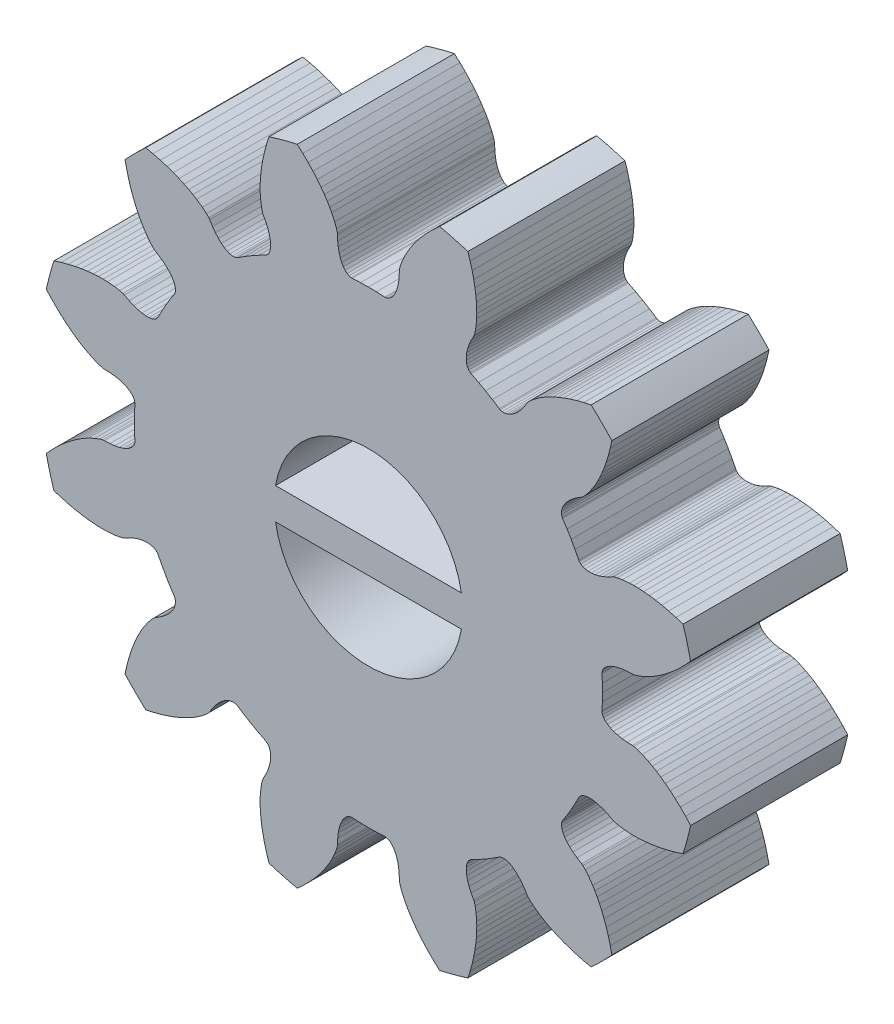
SolidWorks part; units mm, degrees
ref_plane "Płaszczyzna przednia" through (0, 0, 0) normal (0, 0, 1) x (1, 0, 0)
ref_plane "Płaszczyzna górna" through (0, 0, 0) normal (0, 1, 0) x (1, 0, 0)
ref_plane "Płaszczyzna prawa" through (0, 0, 0) normal (1, 0, 0) x (0, 0, -1)
sketch "szkic" plane through (0, 0, 0) normal (0, 0, 1) x (1, 0, 0)
  line L0 (13.3041, -6.8561) -> (13.3646, -6.6243)
  line L1 (13.3646, -6.6243) -> (13.4305, -6.4094)
  line L2 (13.4305, -6.4094) -> (13.5003, -6.2115)
  line L3 (13.5003, -6.2115) -> (13.5727, -6.0307)
  line L4 (13.5727, -6.0307) -> (13.6464, -5.8671)
  line L5 (13.6464, -5.8671) -> (13.7211, -5.718)
  line L6 (13.7211, -5.718) -> (13.7935, -5.5877)
  line L7 (13.7935, -5.5877) -> (13.8642, -5.472)
  line L8 (13.8642, -5.472) -> (13.9934, -5.2871)
  line L9 (13.9934, -5.2871) -> (14.1006, -5.158)
  line L10 (14.1006, -5.158) -> (14.1765, -5.0806)
  line L11 (14.1765, -5.0806) -> (14.2153, -5.0522)
  line L12 (14.2153, -5.0522) -> (14.3621, -4.9616)
  line L13 (14.3621, -4.9616) -> (14.4896, -4.8682)
  line L14 (14.4896, -4.8682) -> (14.5978, -4.7734)
  line L15 (14.5978, -4.7734) -> (14.6868, -4.6788)
  line L16 (14.6868, -4.6788) -> (14.7569, -4.5857)
  line L17 (14.7569, -4.5857) -> (14.8083, -4.4956)
  line L18 (14.8083, -4.4956) -> (14.8415, -4.4098)
  line L19 (14.8415, -4.4098) -> (14.8569, -4.3297)
  line L20 (14.8569, -4.3297) -> (14.8551, -4.2567)
  line L21 (14.8551, -4.2567) -> (14.8367, -4.192)
  line L22 (14.8367, -4.192) -> (14.8215, -4.1631)
  line L23 (14.8215, -4.1631) -> (14.6788, -3.9428)
  line L24 (14.6788, -3.9428) -> (14.5481, -3.725)
  line L25 (14.5481, -3.725) -> (14.4249, -3.5029)
  line L26 (14.4249, -3.5029) -> (14.3054, -3.2691)
  line L27 (14.3054, -3.2691) -> (14.288, -3.2416)
  line L28 (14.288, -3.2416) -> (14.2411, -3.1933)
  line L29 (14.2411, -3.1933) -> (14.1788, -3.1552)
  line L30 (14.1788, -3.1552) -> (14.1017, -3.1285)
  line L31 (14.1017, -3.1285) -> (14.0109, -3.1144)
  line L32 (14.0109, -3.1144) -> (13.9071, -3.1138)
  line L33 (13.9071, -3.1138) -> (13.7915, -3.128)
  line L34 (13.7915, -3.128) -> (13.665, -3.1577)
  line L35 (13.665, -3.1577) -> (13.5289, -3.2041)
  line L36 (13.5289, -3.2041) -> (13.3842, -3.2678)
  line L37 (13.3842, -3.2678) -> (13.2323, -3.3497)
  line L38 (13.2323, -3.3497) -> (13.1884, -3.369)
  line L39 (13.1884, -3.369) -> (13.0833, -3.3961)
  line L40 (13.0833, -3.3961) -> (12.918, -3.4244)
  line L41 (12.918, -3.4244) -> (12.6932, -3.4438)
  line L42 (12.6932, -3.4438) -> (12.5577, -3.4472)
  line L43 (12.5577, -3.4472) -> (12.4086, -3.4447)
  line L44 (12.4086, -3.4447) -> (12.2421, -3.4349)
  line L45 (12.2421, -3.4349) -> (12.0636, -3.4169)
  line L46 (12.0636, -3.4169) -> (11.8708, -3.3892)
  line L47 (11.8708, -3.3892) -> (11.6645, -3.3507)
  line L48 (11.6645, -3.3507) -> (11.4455, -3.3003)
  line L49 (11.4455, -3.3003) -> (11.2145, -3.2368)
  line L50 (11.2145, -3.2368) -> (10.9882, -3.1643)
  line L51 (10.7474, -2.2655) -> (10.9071, -2.0896)
  line L52 (10.9071, -2.0896) -> (11.0754, -1.9191)
  line L53 (11.0754, -1.9191) -> (11.2399, -1.7659)
  line L54 (11.2399, -1.7659) -> (11.3993, -1.6295)
  line L55 (11.3993, -1.6295) -> (11.5524, -1.5091)
  line L56 (11.5524, -1.5091) -> (11.698, -1.4042)
  line L57 (11.698, -1.4042) -> (11.8373, -1.3125)
  line L58 (11.8373, -1.3125) -> (11.9651, -1.2358)
  line L59 (11.9651, -1.2358) -> (12.0842, -1.171)
  line L60 (12.0842, -1.171) -> (12.2886, -1.0754)
  line L61 (12.2886, -1.0754) -> (12.4459, -1.0172)
  line L62 (12.4459, -1.0172) -> (12.5504, -0.9882)
  line L63 (12.5504, -0.9882) -> (12.5981, -0.983)
  line L64 (12.5981, -0.983) -> (12.7706, -0.9779)
  line L65 (12.7706, -0.9779) -> (12.9278, -0.9608)
  line L66 (12.9278, -0.9608) -> (13.0688, -0.9328)
  line L67 (13.0688, -0.9328) -> (13.1933, -0.8953)
  line L68 (13.1933, -0.8953) -> (13.3005, -0.8498)
  line L69 (13.3005, -0.8498) -> (13.3901, -0.7974)
  line L70 (13.3901, -0.7974) -> (13.4617, -0.7397)
  line L71 (13.4617, -0.7397) -> (13.515, -0.6781)
  line L72 (13.515, -0.6781) -> (13.55, -0.6139)
  line L73 (13.55, -0.6139) -> (13.5665, -0.5487)
  line L74 (13.5665, -0.5487) -> (13.5677, -0.5161)
  line L75 (13.5677, -0.5161) -> (13.5543, -0.2539)
  line L76 (13.5543, -0.2539) -> (13.55, 0)
  line L77 (13.55, 0) -> (13.5543, 0.2539)
  line L78 (13.5543, 0.2539) -> (13.5677, 0.5161)
  line L79 (13.5677, 0.5161) -> (13.5665, 0.5487)
  line L80 (13.5665, 0.5487) -> (13.55, 0.6139)
  line L81 (13.55, 0.6139) -> (13.515, 0.6781)
  line L82 (13.515, 0.6781) -> (13.4617, 0.7397)
  line L83 (13.4617, 0.7397) -> (13.3901, 0.7974)
  line L84 (13.3901, 0.7974) -> (13.3005, 0.8498)
  line L85 (13.3005, 0.8498) -> (13.1933, 0.8953)
  line L86 (13.1933, 0.8953) -> (13.0688, 0.9328)
  line L87 (13.0688, 0.9328) -> (12.9278, 0.9608)
  line L88 (12.9278, 0.9608) -> (12.7706, 0.9779)
  line L89 (12.7706, 0.9779) -> (12.5981, 0.983)
  line L90 (12.5981, 0.983) -> (12.5504, 0.9882)
  line L91 (12.5504, 0.9882) -> (12.4459, 1.0172)
  line L92 (12.4459, 1.0172) -> (12.2886, 1.0754)
  line L93 (12.2886, 1.0754) -> (12.0842, 1.171)
  line L94 (12.0842, 1.171) -> (11.9651, 1.2358)
  line L95 (11.9651, 1.2358) -> (11.8373, 1.3125)
  line L96 (11.8373, 1.3125) -> (11.698, 1.4042)
  line L97 (11.698, 1.4042) -> (11.5524, 1.5091)
  line L98 (11.5524, 1.5091) -> (11.3993, 1.6295)
  line L99 (11.3993, 1.6295) -> (11.2399, 1.7659)
  line L100 (11.2399, 1.7659) -> (11.0754, 1.9191)
  line L101 (11.0754, 1.9191) -> (10.9071, 2.0896)
  line L102 (10.9071, 2.0896) -> (10.7474, 2.2655)
  line L103 (10.9882, 3.1643) -> (11.2145, 3.2368)
  line L104 (11.2145, 3.2368) -> (11.4455, 3.3003)
  line L105 (11.4455, 3.3003) -> (11.6645, 3.3507)
  line L106 (11.6645, 3.3507) -> (11.8708, 3.3892)
  line L107 (11.8708, 3.3892) -> (12.0636, 3.4169)
  line L108 (12.0636, 3.4169) -> (12.2421, 3.4349)
  line L109 (12.2421, 3.4349) -> (12.4086, 3.4447)
  line L110 (12.4086, 3.4447) -> (12.5577, 3.4472)
  line L111 (12.5577, 3.4472) -> (12.6932, 3.4438)
  line L112 (12.6932, 3.4438) -> (12.918, 3.4244)
  line L113 (12.918, 3.4244) -> (13.0833, 3.3961)
  line L114 (13.0833, 3.3961) -> (13.1884, 3.369)
  line L115 (13.1884, 3.369) -> (13.2323, 3.3497)
  line L116 (13.2323, 3.3497) -> (13.3842, 3.2678)
  line L117 (13.3842, 3.2678) -> (13.5289, 3.2041)
  line L118 (13.5289, 3.2041) -> (13.665, 3.1577)
  line L119 (13.665, 3.1577) -> (13.7915, 3.128)
  line L120 (13.7915, 3.128) -> (13.9071, 3.1138)
  line L121 (13.9071, 3.1138) -> (14.0109, 3.1144)
  line L122 (14.0109, 3.1144) -> (14.1017, 3.1285)
  line L123 (14.1017, 3.1285) -> (14.1788, 3.1552)
  line L124 (14.1788, 3.1552) -> (14.2411, 3.1933)
  line L125 (14.2411, 3.1933) -> (14.288, 3.2416)
  line L126 (14.288, 3.2416) -> (14.3054, 3.2691)
  line L127 (14.3054, 3.2691) -> (14.4249, 3.5029)
  line L128 (14.4249, 3.5029) -> (14.5481, 3.725)
  line L129 (14.5481, 3.725) -> (14.6788, 3.9428)
  line L130 (14.6788, 3.9428) -> (14.8215, 4.1631)
  line L131 (14.8215, 4.1631) -> (14.8367, 4.192)
  line L132 (14.8367, 4.192) -> (14.8551, 4.2567)
  line L133 (14.8551, 4.2567) -> (14.8569, 4.3297)
  line L134 (14.8569, 4.3297) -> (14.8415, 4.4098)
  line L135 (14.8415, 4.4098) -> (14.8083, 4.4956)
  line L136 (14.8083, 4.4956) -> (14.7569, 4.5857)
  line L137 (14.7569, 4.5857) -> (14.6868, 4.6788)
  line L138 (14.6868, 4.6788) -> (14.5978, 4.7734)
  line L139 (14.5978, 4.7734) -> (14.4896, 4.8682)
  line L140 (14.4896, 4.8682) -> (14.3621, 4.9616)
  line L141 (14.3621, 4.9616) -> (14.2153, 5.0522)
  line L142 (14.2153, 5.0522) -> (14.1765, 5.0806)
  line L143 (14.1765, 5.0806) -> (14.1006, 5.158)
  line L144 (14.1006, 5.158) -> (13.9934, 5.2871)
  line L145 (13.9934, 5.2871) -> (13.8642, 5.472)
  line L146 (13.8642, 5.472) -> (13.7935, 5.5877)
  line L147 (13.7935, 5.5877) -> (13.7211, 5.718)
  line L148 (13.7211, 5.718) -> (13.6464, 5.8671)
  line L149 (13.6464, 5.8671) -> (13.5727, 6.0307)
  line L150 (13.5727, 6.0307) -> (13.5003, 6.2115)
  line L151 (13.5003, 6.2115) -> (13.4305, 6.4094)
  line L152 (13.4305, 6.4094) -> (13.3646, 6.6243)
  line L153 (13.3646, 6.6243) -> (13.3041, 6.8561)
  line L154 (13.3041, 6.8561) -> (13.2537, 7.0883)
  line L155 (13.9117, 7.7463) -> (14.1439, 7.6959)
  line L156 (14.1439, 7.6959) -> (14.3757, 7.6354)
  line L157 (14.3757, 7.6354) -> (14.5906, 7.5695)
  line L158 (14.5906, 7.5695) -> (14.7885, 7.4997)
  line L159 (14.7885, 7.4997) -> (14.9693, 7.4273)
  line L160 (14.9693, 7.4273) -> (15.1329, 7.3536)
  line L161 (15.1329, 7.3536) -> (15.282, 7.2789)
  line L162 (15.282, 7.2789) -> (15.4123, 7.2065)
  line L163 (15.4123, 7.2065) -> (15.528, 7.1358)
  line L164 (15.528, 7.1358) -> (15.7129, 7.0066)
  line L165 (15.7129, 7.0066) -> (15.842, 6.8994)
  line L166 (15.842, 6.8994) -> (15.9194, 6.8235)
  line L167 (15.9194, 6.8235) -> (15.9478, 6.7847)
  line L168 (15.9478, 6.7847) -> (16.0384, 6.6379)
  line L169 (16.0384, 6.6379) -> (16.1318, 6.5104)
  line L170 (16.1318, 6.5104) -> (16.2266, 6.4022)
  line L171 (16.2266, 6.4022) -> (16.3212, 6.3132)
  line L172 (16.3212, 6.3132) -> (16.4143, 6.2431)
  line L173 (16.4143, 6.2431) -> (16.5044, 6.1917)
  line L174 (16.5044, 6.1917) -> (16.5902, 6.1585)
  line L175 (16.5902, 6.1585) -> (16.6703, 6.1431)
  line L176 (16.6703, 6.1431) -> (16.7433, 6.1449)
  line L177 (16.7433, 6.1449) -> (16.808, 6.1633)
  line L178 (16.808, 6.1633) -> (16.8369, 6.1785)
  line L179 (16.8369, 6.1785) -> (17.0572, 6.3212)
  line L180 (17.0572, 6.3212) -> (17.275, 6.4519)
  line L181 (17.275, 6.4519) -> (17.4971, 6.5751)
  line L182 (17.4971, 6.5751) -> (17.7309, 6.6946)
  line L183 (17.7309, 6.6946) -> (17.7584, 6.712)
  line L184 (17.7584, 6.712) -> (17.8067, 6.7589)
  line L185 (17.8067, 6.7589) -> (17.8448, 6.8212)
  line L186 (17.8448, 6.8212) -> (17.8715, 6.8983)
  line L187 (17.8715, 6.8983) -> (17.8856, 6.9891)
  line L188 (17.8856, 6.9891) -> (17.8862, 7.0929)
  line L189 (17.8862, 7.0929) -> (17.872, 7.2085)
  line L190 (17.872, 7.2085) -> (17.8423, 7.335)
  line L191 (17.8423, 7.335) -> (17.7959, 7.4711)
  line L192 (17.7959, 7.4711) -> (17.7322, 7.6158)
  line L193 (17.7322, 7.6158) -> (17.6503, 7.7677)
  line L194 (17.6503, 7.7677) -> (17.631, 7.8116)
  line L195 (17.631, 7.8116) -> (17.6039, 7.9167)
  line L196 (17.6039, 7.9167) -> (17.5756, 8.082)
  line L197 (17.5756, 8.082) -> (17.5562, 8.3068)
  line L198 (17.5562, 8.3068) -> (17.5528, 8.4423)
  line L199 (17.5528, 8.4423) -> (17.5553, 8.5914)
  line L200 (17.5553, 8.5914) -> (17.5651, 8.7579)
  line L201 (17.5651, 8.7579) -> (17.5831, 8.9364)
  line L202 (17.5831, 8.9364) -> (17.6108, 9.1292)
  line L203 (17.6108, 9.1292) -> (17.6493, 9.3355)
  line L204 (17.6493, 9.3355) -> (17.6997, 9.5545)
  line L205 (17.6997, 9.5545) -> (17.7632, 9.7855)
  line L206 (17.7632, 9.7855) -> (17.8357, 10.0118)
  line L207 (18.7345, 10.2526) -> (18.9104, 10.0929)
  line L208 (18.9104, 10.0929) -> (19.0809, 9.9246)
  line L209 (19.0809, 9.9246) -> (19.2341, 9.7601)
  line L210 (19.2341, 9.7601) -> (19.3706, 9.6007)
  line L211 (19.3706, 9.6007) -> (19.4909, 9.4476)
  line L212 (19.4909, 9.4476) -> (19.5958, 9.302)
  line L213 (19.5958, 9.302) -> (19.6875, 9.1627)
  line L214 (19.6875, 9.1627) -> (19.7642, 9.0349)
  line L215 (19.7642, 9.0349) -> (19.829, 8.9158)
  line L216 (19.829, 8.9158) -> (19.9246, 8.7114)
  line L217 (19.9246, 8.7114) -> (19.9828, 8.5541)
  line L218 (19.9828, 8.5541) -> (20.0118, 8.4496)
  line L219 (20.0118, 8.4496) -> (20.017, 8.4019)
  line L220 (20.017, 8.4019) -> (20.0221, 8.2294)
  line L221 (20.0221, 8.2294) -> (20.0392, 8.0722)
  line L222 (20.0392, 8.0722) -> (20.0672, 7.9311)
  line L223 (20.0672, 7.9311) -> (20.1046, 7.8068)
  line L224 (20.1046, 7.8068) -> (20.1502, 7.6995)
  line L225 (20.1502, 7.6995) -> (20.2026, 7.61)
  line L226 (20.2026, 7.61) -> (20.2603, 7.5383)
  line L227 (20.2603, 7.5383) -> (20.3219, 7.485)
  line L228 (20.3219, 7.485) -> (20.3861, 7.45)
  line L229 (20.3861, 7.45) -> (20.4513, 7.4335)
  line L230 (20.4513, 7.4335) -> (20.4839, 7.4323)
  line L231 (20.4839, 7.4323) -> (20.7461, 7.4457)
  line L232 (20.7461, 7.4457) -> (21, 7.45)
  line L233 (21, 7.45) -> (21.2539, 7.4457)
  line L234 (21.2539, 7.4457) -> (21.5161, 7.4323)
  line L235 (21.5161, 7.4323) -> (21.5487, 7.4335)
  line L236 (21.5487, 7.4335) -> (21.6139, 7.45)
  line L237 (21.6139, 7.45) -> (21.6781, 7.485)
  line L238 (21.6781, 7.485) -> (21.7397, 7.5383)
  line L239 (21.7397, 7.5383) -> (21.7974, 7.61)
  line L240 (21.7974, 7.61) -> (21.8498, 7.6995)
  line L241 (21.8498, 7.6995) -> (21.8954, 7.8068)
  line L242 (21.8954, 7.8068) -> (21.9328, 7.9311)
  line L243 (21.9328, 7.9311) -> (21.9608, 8.0722)
  line L244 (21.9608, 8.0722) -> (21.9779, 8.2294)
  line L245 (21.9779, 8.2294) -> (21.983, 8.4019)
  line L246 (21.983, 8.4019) -> (21.9882, 8.4496)
  line L247 (21.9882, 8.4496) -> (22.0172, 8.5541)
  line L248 (22.0172, 8.5541) -> (22.0754, 8.7114)
  line L249 (22.0754, 8.7114) -> (22.171, 8.9158)
  line L250 (22.171, 8.9158) -> (22.2358, 9.0349)
  line L251 (22.2358, 9.0349) -> (22.3125, 9.1627)
  line L252 (22.3125, 9.1627) -> (22.4042, 9.302)
  line L253 (22.4042, 9.302) -> (22.5091, 9.4476)
  line L254 (22.5091, 9.4476) -> (22.6294, 9.6007)
  line L255 (22.6294, 9.6007) -> (22.7659, 9.7601)
  line L256 (22.7659, 9.7601) -> (22.9191, 9.9246)
  line L257 (22.9191, 9.9246) -> (23.0896, 10.0929)
  line L258 (23.0896, 10.0929) -> (23.2655, 10.2526)
  line L259 (24.1643, 10.0118) -> (24.2368, 9.7855)
  line L260 (24.2368, 9.7855) -> (24.3003, 9.5545)
  line L261 (24.3003, 9.5545) -> (24.3507, 9.3355)
  line L262 (24.3507, 9.3355) -> (24.3892, 9.1292)
  line L263 (24.3892, 9.1292) -> (24.4169, 8.9364)
  line L264 (24.4169, 8.9364) -> (24.4349, 8.7579)
  line L265 (24.4349, 8.7579) -> (24.4447, 8.5914)
  line L266 (24.4447, 8.5914) -> (24.4472, 8.4423)
  line L267 (24.4472, 8.4423) -> (24.4438, 8.3068)
  line L268 (24.4438, 8.3068) -> (24.4244, 8.082)
  line L269 (24.4244, 8.082) -> (24.3961, 7.9167)
  line L270 (24.3961, 7.9167) -> (24.369, 7.8116)
  line L271 (24.369, 7.8116) -> (24.3497, 7.7677)
  line L272 (24.3497, 7.7677) -> (24.2678, 7.6158)
  line L273 (24.2678, 7.6158) -> (24.2041, 7.4711)
  line L274 (24.2041, 7.4711) -> (24.1577, 7.335)
  line L275 (24.1577, 7.335) -> (24.128, 7.2085)
  line L276 (24.128, 7.2085) -> (24.1138, 7.0929)
  line L277 (24.1138, 7.0929) -> (24.1144, 6.9891)
  line L278 (24.1144, 6.9891) -> (24.1285, 6.8983)
  line L279 (24.1285, 6.8983) -> (24.1552, 6.8212)
  line L280 (24.1552, 6.8212) -> (24.1933, 6.7589)
  line L281 (24.1933, 6.7589) -> (24.2416, 6.712)
  line L282 (24.2416, 6.712) -> (24.2691, 6.6946)
  line L283 (24.2691, 6.6946) -> (24.5029, 6.5751)
  line L284 (24.5029, 6.5751) -> (24.725, 6.4519)
  line L285 (24.725, 6.4519) -> (24.9428, 6.3212)
  line L286 (24.9428, 6.3212) -> (25.1631, 6.1785)
  line L287 (25.1631, 6.1785) -> (25.192, 6.1633)
  line L288 (25.192, 6.1633) -> (25.2567, 6.1449)
  line L289 (25.2567, 6.1449) -> (25.3297, 6.1431)
  line L290 (25.3297, 6.1431) -> (25.4098, 6.1585)
  line L291 (25.4098, 6.1585) -> (25.4956, 6.1917)
  line L292 (25.4956, 6.1917) -> (25.5857, 6.2431)
  line L293 (25.5857, 6.2431) -> (25.6788, 6.3132)
  line L294 (25.6788, 6.3132) -> (25.7734, 6.4022)
  line L295 (25.7734, 6.4022) -> (25.8682, 6.5104)
  line L296 (25.8682, 6.5104) -> (25.9616, 6.6379)
  line L297 (25.9616, 6.6379) -> (26.0522, 6.7847)
  line L298 (26.0522, 6.7847) -> (26.0806, 6.8235)
  line L299 (26.0806, 6.8235) -> (26.158, 6.8994)
  line L300 (26.158, 6.8994) -> (26.2871, 7.0066)
  line L301 (26.2871, 7.0066) -> (26.472, 7.1358)
  line L302 (26.472, 7.1358) -> (26.5877, 7.2065)
  line L303 (26.5877, 7.2065) -> (26.718, 7.2789)
  line L304 (26.718, 7.2789) -> (26.8671, 7.3536)
  line L305 (26.8671, 7.3536) -> (27.0307, 7.4273)
  line L306 (27.0307, 7.4273) -> (27.2115, 7.4997)
  line L307 (27.2115, 7.4997) -> (27.4094, 7.5695)
  line L308 (27.4094, 7.5695) -> (27.6243, 7.6354)
  line L309 (27.6243, 7.6354) -> (27.8561, 7.6959)
  line L310 (27.8561, 7.6959) -> (28.0883, 7.7463)
  line L311 (28.7463, 7.0883) -> (28.6959, 6.8561)
  line L312 (28.6959, 6.8561) -> (28.6354, 6.6243)
  line L313 (28.6354, 6.6243) -> (28.5695, 6.4094)
  line L314 (28.5695, 6.4094) -> (28.4997, 6.2115)
  line L315 (28.4997, 6.2115) -> (28.4273, 6.0307)
  line L316 (28.4273, 6.0307) -> (28.3536, 5.8671)
  line L317 (28.3536, 5.8671) -> (28.2789, 5.718)
  line L318 (28.2789, 5.718) -> (28.2065, 5.5877)
  line L319 (28.2065, 5.5877) -> (28.1358, 5.472)
  line L320 (28.1358, 5.472) -> (28.0066, 5.2871)
  line L321 (28.0066, 5.2871) -> (27.8994, 5.158)
  line L322 (27.8994, 5.158) -> (27.8235, 5.0806)
  line L323 (27.8235, 5.0806) -> (27.7847, 5.0522)
  line L324 (27.7847, 5.0522) -> (27.6379, 4.9616)
  line L325 (27.6379, 4.9616) -> (27.5104, 4.8682)
  line L326 (27.5104, 4.8682) -> (27.4022, 4.7734)
  line L327 (27.4022, 4.7734) -> (27.3132, 4.6788)
  line L328 (27.3132, 4.6788) -> (27.2431, 4.5857)
  line L329 (27.2431, 4.5857) -> (27.1917, 4.4956)
  line L330 (27.1917, 4.4956) -> (27.1585, 4.4098)
  line L331 (27.1585, 4.4098) -> (27.1431, 4.3297)
  line L332 (27.1431, 4.3297) -> (27.1449, 4.2567)
  line L333 (27.1449, 4.2567) -> (27.1633, 4.192)
  line L334 (27.1633, 4.192) -> (27.1785, 4.1631)
  line L335 (27.1785, 4.1631) -> (27.3212, 3.9428)
  line L336 (27.3212, 3.9428) -> (27.4519, 3.725)
  line L337 (27.4519, 3.725) -> (27.5751, 3.5029)
  line L338 (27.5751, 3.5029) -> (27.6946, 3.2691)
  line L339 (27.6946, 3.2691) -> (27.712, 3.2416)
  line L340 (27.712, 3.2416) -> (27.7589, 3.1933)
  line L341 (27.7589, 3.1933) -> (27.8212, 3.1552)
  line L342 (27.8212, 3.1552) -> (27.8983, 3.1285)
  line L343 (27.8983, 3.1285) -> (27.9891, 3.1144)
  line L344 (27.9891, 3.1144) -> (28.0929, 3.1138)
  line L345 (28.0929, 3.1138) -> (28.2085, 3.128)
  line L346 (28.2085, 3.128) -> (28.335, 3.1577)
  line L347 (28.335, 3.1577) -> (28.4711, 3.2041)
  line L348 (28.4711, 3.2041) -> (28.6158, 3.2678)
  line L349 (28.6158, 3.2678) -> (28.7677, 3.3497)
  line L350 (28.7677, 3.3497) -> (28.8116, 3.369)
  line L351 (28.8116, 3.369) -> (28.9167, 3.3961)
  line L352 (28.9167, 3.3961) -> (29.082, 3.4244)
  line L353 (29.082, 3.4244) -> (29.3068, 3.4438)
  line L354 (29.3068, 3.4438) -> (29.4423, 3.4472)
  line L355 (29.4423, 3.4472) -> (29.5914, 3.4447)
  line L356 (29.5914, 3.4447) -> (29.7579, 3.4349)
  line L357 (29.7579, 3.4349) -> (29.9364, 3.4169)
  line L358 (29.9364, 3.4169) -> (30.1292, 3.3892)
  line L359 (30.1292, 3.3892) -> (30.3355, 3.3507)
  line L360 (30.3355, 3.3507) -> (30.5545, 3.3003)
  line L361 (30.5545, 3.3003) -> (30.7855, 3.2368)
  line L362 (30.7855, 3.2368) -> (31.0118, 3.1643)
  line L363 (31.2526, 2.2655) -> (31.0929, 2.0896)
  line L364 (31.0929, 2.0896) -> (30.9246, 1.9191)
  line L365 (30.9246, 1.9191) -> (30.7601, 1.7659)
  line L366 (30.7601, 1.7659) -> (30.6007, 1.6295)
  line L367 (30.6007, 1.6295) -> (30.4476, 1.5091)
  line L368 (30.4476, 1.5091) -> (30.302, 1.4042)
  line L369 (30.302, 1.4042) -> (30.1627, 1.3125)
  line L370 (30.1627, 1.3125) -> (30.0349, 1.2358)
  line L371 (30.0349, 1.2358) -> (29.9158, 1.171)
  line L372 (29.9158, 1.171) -> (29.7114, 1.0754)
  line L373 (29.7114, 1.0754) -> (29.5541, 1.0172)
  line L374 (29.5541, 1.0172) -> (29.4496, 0.9882)
  line L375 (29.4496, 0.9882) -> (29.4019, 0.983)
  line L376 (29.4019, 0.983) -> (29.2294, 0.9779)
  line L377 (29.2294, 0.9779) -> (29.0722, 0.9608)
  line L378 (29.0722, 0.9608) -> (28.9311, 0.9328)
  line L379 (28.9311, 0.9328) -> (28.8068, 0.8953)
  line L380 (28.8068, 0.8953) -> (28.6995, 0.8498)
  line L381 (28.6995, 0.8498) -> (28.61, 0.7974)
  line L382 (28.61, 0.7974) -> (28.5383, 0.7397)
  line L383 (28.5383, 0.7397) -> (28.485, 0.6781)
  line L384 (28.485, 0.6781) -> (28.45, 0.6139)
  line L385 (28.45, 0.6139) -> (28.4335, 0.5487)
  line L386 (28.4335, 0.5487) -> (28.4323, 0.5161)
  line L387 (28.4323, 0.5161) -> (28.4457, 0.2539)
  line L388 (28.4457, 0.2539) -> (28.45, 0)
  line L389 (28.45, 0) -> (28.4457, -0.2539)
  line L390 (28.4457, -0.2539) -> (28.4323, -0.5161)
  line L391 (28.4323, -0.5161) -> (28.4335, -0.5487)
  line L392 (28.4335, -0.5487) -> (28.45, -0.6139)
  line L393 (28.45, -0.6139) -> (28.485, -0.6781)
  line L394 (28.485, -0.6781) -> (28.5383, -0.7397)
  line L395 (28.5383, -0.7397) -> (28.61, -0.7974)
  line L396 (28.61, -0.7974) -> (28.6995, -0.8498)
  line L397 (28.6995, -0.8498) -> (28.8068, -0.8953)
  line L398 (28.8068, -0.8953) -> (28.9311, -0.9328)
  line L399 (28.9311, -0.9328) -> (29.0722, -0.9608)
  line L400 (29.0722, -0.9608) -> (29.2294, -0.9779)
  line L401 (29.2294, -0.9779) -> (29.4019, -0.983)
  line L402 (29.4019, -0.983) -> (29.4496, -0.9882)
  line L403 (29.4496, -0.9882) -> (29.5541, -1.0172)
  line L404 (29.5541, -1.0172) -> (29.7114, -1.0754)
  line L405 (29.7114, -1.0754) -> (29.9158, -1.171)
  line L406 (29.9158, -1.171) -> (30.0349, -1.2358)
  line L407 (30.0349, -1.2358) -> (30.1627, -1.3125)
  line L408 (30.1627, -1.3125) -> (30.302, -1.4042)
  line L409 (30.302, -1.4042) -> (30.4476, -1.5091)
  line L410 (30.4476, -1.5091) -> (30.6007, -1.6295)
  line L411 (30.6007, -1.6295) -> (30.7601, -1.7659)
  line L412 (30.7601, -1.7659) -> (30.9246, -1.9191)
  line L413 (30.9246, -1.9191) -> (31.0929, -2.0896)
  line L414 (31.0929, -2.0896) -> (31.2526, -2.2655)
  line L415 (31.0118, -3.1643) -> (30.7855, -3.2368)
  line L416 (30.7855, -3.2368) -> (30.5545, -3.3003)
  line L417 (30.5545, -3.3003) -> (30.3355, -3.3507)
  line L418 (30.3355, -3.3507) -> (30.1292, -3.3892)
  line L419 (30.1292, -3.3892) -> (29.9364, -3.4169)
  line L420 (29.9364, -3.4169) -> (29.7579, -3.4349)
  line L421 (29.7579, -3.4349) -> (29.5914, -3.4447)
  line L422 (29.5914, -3.4447) -> (29.4423, -3.4472)
  line L423 (29.4423, -3.4472) -> (29.3068, -3.4438)
  line L424 (29.3068, -3.4438) -> (29.082, -3.4244)
  line L425 (29.082, -3.4244) -> (28.9167, -3.3961)
  line L426 (28.9167, -3.3961) -> (28.8116, -3.369)
  line L427 (28.8116, -3.369) -> (28.7677, -3.3497)
  line L428 (28.7677, -3.3497) -> (28.6158, -3.2678)
  line L429 (28.6158, -3.2678) -> (28.4711, -3.2041)
  line L430 (28.4711, -3.2041) -> (28.335, -3.1577)
  line L431 (28.335, -3.1577) -> (28.2085, -3.128)
  line L432 (28.2085, -3.128) -> (28.0929, -3.1138)
  line L433 (28.0929, -3.1138) -> (27.9891, -3.1144)
  line L434 (27.9891, -3.1144) -> (27.8983, -3.1285)
  line L435 (27.8983, -3.1285) -> (27.8212, -3.1552)
  line L436 (27.8212, -3.1552) -> (27.7589, -3.1933)
  line L437 (27.7589, -3.1933) -> (27.712, -3.2416)
  line L438 (27.712, -3.2416) -> (27.6946, -3.2691)
  line L439 (27.6946, -3.2691) -> (27.5751, -3.5029)
  line L440 (27.5751, -3.5029) -> (27.4519, -3.725)
  line L441 (27.4519, -3.725) -> (27.3212, -3.9428)
  line L442 (27.3212, -3.9428) -> (27.1785, -4.1631)
  line L443 (27.1785, -4.1631) -> (27.1633, -4.192)
  line L444 (27.1633, -4.192) -> (27.1449, -4.2567)
  line L445 (27.1449, -4.2567) -> (27.1431, -4.3297)
  line L446 (27.1431, -4.3297) -> (27.1585, -4.4098)
  line L447 (27.1585, -4.4098) -> (27.1917, -4.4956)
  line L448 (27.1917, -4.4956) -> (27.2431, -4.5857)
  line L449 (27.2431, -4.5857) -> (27.3132, -4.6788)
  line L450 (27.3132, -4.6788) -> (27.4022, -4.7734)
  line L451 (27.4022, -4.7734) -> (27.5104, -4.8682)
  line L452 (27.5104, -4.8682) -> (27.6379, -4.9616)
  line L453 (27.6379, -4.9616) -> (27.7847, -5.0522)
  line L454 (27.7847, -5.0522) -> (27.8235, -5.0806)
  line L455 (27.8235, -5.0806) -> (27.8994, -5.158)
  line L456 (27.8994, -5.158) -> (28.0066, -5.2871)
  line L457 (28.0066, -5.2871) -> (28.1358, -5.472)
  line L458 (28.1358, -5.472) -> (28.2065, -5.5877)
  line L459 (28.2065, -5.5877) -> (28.2789, -5.718)
  line L460 (28.2789, -5.718) -> (28.3536, -5.8671)
  line L461 (28.3536, -5.8671) -> (28.4273, -6.0307)
  line L462 (28.4273, -6.0307) -> (28.4997, -6.2115)
  line L463 (28.4997, -6.2115) -> (28.5695, -6.4094)
  line L464 (28.5695, -6.4094) -> (28.6354, -6.6243)
  line L465 (28.6354, -6.6243) -> (28.6959, -6.8561)
  line L466 (28.6959, -6.8561) -> (28.7463, -7.0883)
  line L467 (28.0883, -7.7463) -> (27.8561, -7.6959)
  line L468 (27.8561, -7.6959) -> (27.6243, -7.6354)
  line L469 (27.6243, -7.6354) -> (27.4094, -7.5695)
  line L470 (27.4094, -7.5695) -> (27.2115, -7.4997)
  line L471 (27.2115, -7.4997) -> (27.0307, -7.4273)
  line L472 (27.0307, -7.4273) -> (26.8671, -7.3536)
  line L473 (26.8671, -7.3536) -> (26.718, -7.2789)
  line L474 (26.718, -7.2789) -> (26.5877, -7.2065)
  line L475 (26.5877, -7.2065) -> (26.472, -7.1358)
  line L476 (26.472, -7.1358) -> (26.2871, -7.0066)
  line L477 (26.2871, -7.0066) -> (26.158, -6.8994)
  line L478 (26.158, -6.8994) -> (26.0806, -6.8235)
  line L479 (26.0806, -6.8235) -> (26.0522, -6.7847)
  line L480 (26.0522, -6.7847) -> (25.9616, -6.6379)
  line L481 (25.9616, -6.6379) -> (25.8682, -6.5104)
  line L482 (25.8682, -6.5104) -> (25.7734, -6.4022)
  line L483 (25.7734, -6.4022) -> (25.6788, -6.3132)
  line L484 (25.6788, -6.3132) -> (25.5857, -6.2431)
  line L485 (25.5857, -6.2431) -> (25.4956, -6.1917)
  line L486 (25.4956, -6.1917) -> (25.4098, -6.1585)
  line L487 (25.4098, -6.1585) -> (25.3297, -6.1431)
  line L488 (25.3297, -6.1431) -> (25.2567, -6.1449)
  line L489 (25.2567, -6.1449) -> (25.192, -6.1633)
  line L490 (25.192, -6.1633) -> (25.1631, -6.1785)
  line L491 (25.1631, -6.1785) -> (24.9428, -6.3212)
  line L492 (24.9428, -6.3212) -> (24.725, -6.4519)
  line L493 (24.725, -6.4519) -> (24.5029, -6.5751)
  line L494 (24.5029, -6.5751) -> (24.2691, -6.6946)
  line L495 (24.2691, -6.6946) -> (24.2416, -6.712)
  line L496 (24.2416, -6.712) -> (24.1933, -6.7589)
  line L497 (24.1933, -6.7589) -> (24.1552, -6.8212)
  line L498 (24.1552, -6.8212) -> (24.1285, -6.8983)
  line L499 (24.1285, -6.8983) -> (24.1144, -6.9891)
  line L500 (24.1144, -6.9891) -> (24.1138, -7.0929)
  line L501 (24.1138, -7.0929) -> (24.128, -7.2085)
  line L502 (24.128, -7.2085) -> (24.1577, -7.335)
  line L503 (24.1577, -7.335) -> (24.2041, -7.4711)
  line L504 (24.2041, -7.4711) -> (24.2678, -7.6158)
  line L505 (24.2678, -7.6158) -> (24.3497, -7.7677)
  line L506 (24.3497, -7.7677) -> (24.369, -7.8116)
  line L507 (24.369, -7.8116) -> (24.3961, -7.9167)
  line L508 (24.3961, -7.9167) -> (24.4244, -8.082)
  line L509 (24.4244, -8.082) -> (24.4438, -8.3068)
  line L510 (24.4438, -8.3068) -> (24.4472, -8.4423)
  line L511 (24.4472, -8.4423) -> (24.4447, -8.5914)
  line L512 (24.4447, -8.5914) -> (24.4349, -8.7579)
  line L513 (24.4349, -8.7579) -> (24.4169, -8.9364)
  line L514 (24.4169, -8.9364) -> (24.3892, -9.1292)
  line L515 (24.3892, -9.1292) -> (24.3507, -9.3355)
  line L516 (24.3507, -9.3355) -> (24.3003, -9.5545)
  line L517 (24.3003, -9.5545) -> (24.2368, -9.7855)
  line L518 (24.2368, -9.7855) -> (24.1643, -10.0118)
  line L519 (23.2655, -10.2526) -> (23.0896, -10.0929)
  line L520 (23.0896, -10.0929) -> (22.9191, -9.9246)
  line L521 (22.9191, -9.9246) -> (22.7659, -9.7601)
  line L522 (22.7659, -9.7601) -> (22.6294, -9.6007)
  line L523 (22.6294, -9.6007) -> (22.5091, -9.4476)
  line L524 (22.5091, -9.4476) -> (22.4042, -9.302)
  line L525 (22.4042, -9.302) -> (22.3125, -9.1627)
  line L526 (22.3125, -9.1627) -> (22.2358, -9.0349)
  line L527 (22.2358, -9.0349) -> (22.171, -8.9158)
  line L528 (22.171, -8.9158) -> (22.0754, -8.7114)
  line L529 (22.0754, -8.7114) -> (22.0172, -8.5541)
  line L530 (22.0172, -8.5541) -> (21.9882, -8.4496)
  line L531 (21.9882, -8.4496) -> (21.983, -8.4019)
  line L532 (21.983, -8.4019) -> (21.9779, -8.2294)
  line L533 (21.9779, -8.2294) -> (21.9608, -8.0722)
  line L534 (21.9608, -8.0722) -> (21.9328, -7.9311)
  line L535 (21.9328, -7.9311) -> (21.8954, -7.8068)
  line L536 (21.8954, -7.8068) -> (21.8498, -7.6995)
  line L537 (21.8498, -7.6995) -> (21.7974, -7.61)
  line L538 (21.7974, -7.61) -> (21.7397, -7.5383)
  line L539 (21.7397, -7.5383) -> (21.6781, -7.485)
  line L540 (21.6781, -7.485) -> (21.6139, -7.45)
  line L541 (21.6139, -7.45) -> (21.5487, -7.4335)
  line L542 (21.5487, -7.4335) -> (21.5161, -7.4323)
  line L543 (21.5161, -7.4323) -> (21.2539, -7.4457)
  line L544 (21.2539, -7.4457) -> (21, -7.45)
  line L545 (21, -7.45) -> (20.7461, -7.4457)
  line L546 (20.7461, -7.4457) -> (20.4839, -7.4323)
  line L547 (20.4839, -7.4323) -> (20.4513, -7.4335)
  line L548 (20.4513, -7.4335) -> (20.3861, -7.45)
  line L549 (20.3861, -7.45) -> (20.3219, -7.485)
  line L550 (20.3219, -7.485) -> (20.2603, -7.5383)
  line L551 (20.2603, -7.5383) -> (20.2026, -7.61)
  line L552 (20.2026, -7.61) -> (20.1502, -7.6995)
  line L553 (20.1502, -7.6995) -> (20.1046, -7.8068)
  line L554 (20.1046, -7.8068) -> (20.0672, -7.9311)
  line L555 (20.0672, -7.9311) -> (20.0392, -8.0722)
  line L556 (20.0392, -8.0722) -> (20.0221, -8.2294)
  line L557 (20.0221, -8.2294) -> (20.017, -8.4019)
  line L558 (20.017, -8.4019) -> (20.0118, -8.4496)
  line L559 (20.0118, -8.4496) -> (19.9828, -8.5541)
  line L560 (19.9828, -8.5541) -> (19.9246, -8.7114)
  line L561 (19.9246, -8.7114) -> (19.829, -8.9158)
  line L562 (19.829, -8.9158) -> (19.7642, -9.0349)
  line L563 (19.7642, -9.0349) -> (19.6875, -9.1627)
  line L564 (19.6875, -9.1627) -> (19.5958, -9.302)
  line L565 (19.5958, -9.302) -> (19.4909, -9.4476)
  line L566 (19.4909, -9.4476) -> (19.3706, -9.6007)
  line L567 (19.3706, -9.6007) -> (19.2341, -9.7601)
  line L568 (19.2341, -9.7601) -> (19.0809, -9.9246)
  line L569 (19.0809, -9.9246) -> (18.9104, -10.0929)
  line L570 (18.9104, -10.0929) -> (18.7345, -10.2526)
  line L571 (17.8357, -10.0118) -> (17.7632, -9.7855)
  line L572 (17.7632, -9.7855) -> (17.6997, -9.5545)
  line L573 (17.6997, -9.5545) -> (17.6493, -9.3355)
  line L574 (17.6493, -9.3355) -> (17.6108, -9.1292)
  line L575 (17.6108, -9.1292) -> (17.5831, -8.9364)
  line L576 (17.5831, -8.9364) -> (17.5651, -8.7579)
  line L577 (17.5651, -8.7579) -> (17.5553, -8.5914)
  line L578 (17.5553, -8.5914) -> (17.5528, -8.4423)
  line L579 (17.5528, -8.4423) -> (17.5562, -8.3068)
  line L580 (17.5562, -8.3068) -> (17.5756, -8.082)
  line L581 (17.5756, -8.082) -> (17.6039, -7.9167)
  line L582 (17.6039, -7.9167) -> (17.631, -7.8116)
  line L583 (17.631, -7.8116) -> (17.6503, -7.7677)
  line L584 (17.6503, -7.7677) -> (17.7322, -7.6158)
  line L585 (17.7322, -7.6158) -> (17.7959, -7.4711)
  line L586 (17.7959, -7.4711) -> (17.8423, -7.335)
  line L587 (17.8423, -7.335) -> (17.872, -7.2085)
  line L588 (17.872, -7.2085) -> (17.8862, -7.0929)
  line L589 (17.8862, -7.0929) -> (17.8856, -6.9891)
  line L590 (17.8856, -6.9891) -> (17.8715, -6.8983)
  line L591 (17.8715, -6.8983) -> (17.8448, -6.8212)
  line L592 (17.8448, -6.8212) -> (17.8067, -6.7589)
  line L593 (17.8067, -6.7589) -> (17.7584, -6.712)
  line L594 (17.7584, -6.712) -> (17.7309, -6.6946)
  line L595 (17.7309, -6.6946) -> (17.4971, -6.5751)
  line L596 (17.4971, -6.5751) -> (17.275, -6.4519)
  line L597 (17.275, -6.4519) -> (17.0572, -6.3212)
  line L598 (17.0572, -6.3212) -> (16.8369, -6.1785)
  line L599 (16.8369, -6.1785) -> (16.808, -6.1633)
  line L600 (16.808, -6.1633) -> (16.7433, -6.1449)
  line L601 (16.7433, -6.1449) -> (16.6703, -6.1431)
  line L602 (16.6703, -6.1431) -> (16.5902, -6.1585)
  line L603 (16.5902, -6.1585) -> (16.5044, -6.1917)
  line L604 (16.5044, -6.1917) -> (16.4143, -6.2431)
  line L605 (16.4143, -6.2431) -> (16.3212, -6.3132)
  line L606 (16.3212, -6.3132) -> (16.2266, -6.4022)
  line L607 (16.2266, -6.4022) -> (16.1318, -6.5104)
  line L608 (16.1318, -6.5104) -> (16.0384, -6.6379)
  line L609 (16.0384, -6.6379) -> (15.9478, -6.7847)
  line L610 (15.9478, -6.7847) -> (15.9194, -6.8235)
  line L611 (15.9194, -6.8235) -> (15.842, -6.8994)
  line L612 (15.842, -6.8994) -> (15.7129, -7.0066)
  line L613 (15.7129, -7.0066) -> (15.528, -7.1358)
  line L614 (15.528, -7.1358) -> (15.4123, -7.2065)
  line L615 (15.4123, -7.2065) -> (15.282, -7.2789)
  line L616 (15.282, -7.2789) -> (15.1329, -7.3536)
  line L617 (15.1329, -7.3536) -> (14.9693, -7.4273)
  line L618 (14.9693, -7.4273) -> (14.7885, -7.4997)
  line L619 (14.7885, -7.4997) -> (14.5906, -7.5695)
  line L620 (14.5906, -7.5695) -> (14.3757, -7.6354)
  line L621 (14.3757, -7.6354) -> (14.1439, -7.6959)
  line L622 (14.1439, -7.6959) -> (13.9117, -7.7463)
  line L623 (13.2537, -7.0883) -> (13.3041, -6.8561)
  line L627 (20.2026, 0.5) -> (23.958, 0.5) construction
  line L628 (23.958, 0.5) -> (18.042, 0.5) construction
  line L629 (20.2026, -0.5) -> (23.958, -0.5) construction
  line L630 (23.958, -0.5) -> (18.042, -0.5) construction
  line L631 (18.042, 0.5) -> (23.958, 0.5)
  line L632 (18.042, -0.5) -> (23.958, -0.5)
  arc A0 (18.042, -0.5) -> (23.958, -0.5) centre (21, 0) ccw
  arc A1 (23.958, 0.5) -> (18.042, 0.5) centre (21, 0) ccw
  arc A2 (10.7474, -2.2655) -> (10.9882, -3.1643) centre (21, 0) ccw
  arc A3 (10.9882, 3.1643) -> (10.7474, 2.2655) centre (21, 0) ccw
  arc A4 (13.9117, 7.7463) -> (13.2537, 7.0883) centre (21, 0) ccw
  arc A5 (18.7345, 10.2526) -> (17.8357, 10.0118) centre (21, 0) ccw
  arc A6 (24.1643, 10.0118) -> (23.2655, 10.2526) centre (21, 0) ccw
  arc A7 (28.7463, 7.0883) -> (28.0883, 7.7463) centre (21, 0) ccw
  arc A8 (31.2526, 2.2655) -> (31.0118, 3.1643) centre (21, 0) ccw
  arc A9 (31.0118, -3.1643) -> (31.2526, -2.2655) centre (21, 0) ccw
  arc A10 (28.0883, -7.7463) -> (28.7463, -7.0883) centre (21, 0) ccw
  arc A11 (23.2655, -10.2526) -> (24.1643, -10.0118) centre (21, 0) ccw
  arc A12 (17.8357, -10.0118) -> (18.7345, -10.2526) centre (21, 0) ccw
  arc A13 (13.2537, -7.0883) -> (13.9117, -7.7463) centre (21, 0) ccw
  dimension "D1" = 6
extrude "Dodanie-wyciągnięcie1" add sketch "szkic" along normal blind 5
